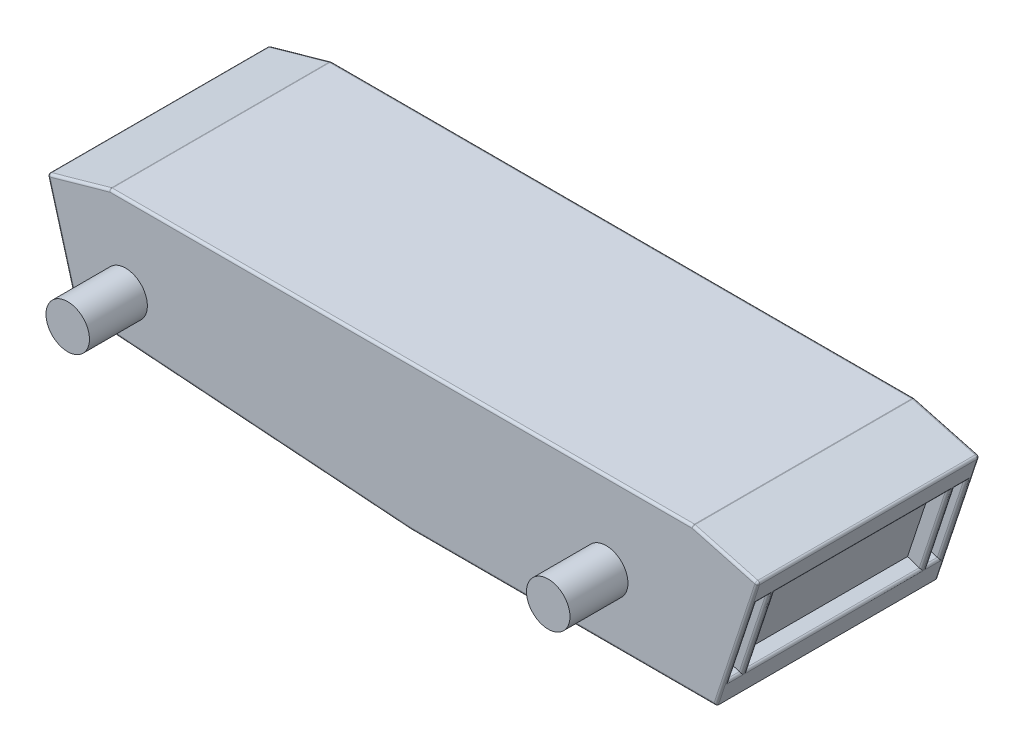
SolidWorks part; units mm, degrees
ref_plane "Front Plane" through (0, 0, 0) normal (0, 0, 1) x (1, 0, 0)
ref_plane "Top Plane" through (0, 0, 0) normal (0, 1, 0) x (1, 0, 0)
ref_plane "Right Plane" through (0, 0, 0) normal (1, 0, 0) x (0, 0, -1)
sketch "Sketch1" plane through (0, 0, 0) normal (0, 0, 1) x (1, 0, 0)
  line L0 (-342.4568, 3.8221) -> (442.8765, 3.8221) construction
sketch "Sketch2" plane through (0, 0, 0) normal (1, 0, 0) x (0, 0, -1)
  line L0 (-168.6601, 20.0355) -> (30.6732, 20.0355) construction
sketch "Sketch3" plane through (0, 0, 0) normal (0, 0, 1) x (1, 0, 0)
  line L0 (412.3453, 143.1765) -> (343.4293, 161.6913)
  line L1 (343.4293, 161.6913) -> (-269.6146, 161.6913)
  line L2 (-269.6146, 161.6913) -> (-335.4449, 143.1765)
  line L3 (-335.4449, 143.1765) -> (-304.9165, 34.6311)
  line L4 (-304.9165, 34.6311) -> (47.1933, 9.4589)
  line L5 (47.1933, 9.4589) -> (368.1156, 9.4589)
  line L6 (368.1156, 9.4589) -> (412.3453, 143.1765)
extrude "Boss-Extrude1" add sketch "Sketch3" along normal blind 116.84 and the other way blind 116.84
sketch "Sketch4" plane through (328.9924, -108.8206, 0) normal (0.9494, -0.314, 0) x (0, 0, -1)
  line L0 (-97.79, 240.0246) -> (-110.49, 240.0246)
  line L2 (-110.49, 240.0246) -> (-104.14, 240.0246)
  line L3 (-110.49, 240.0246) -> (-110.49, 149.9819)
  line L4 (-97.79, 149.9819) -> (-110.49, 149.9819)
  line L5 (-104.14, 240.0246) -> (-97.79, 240.0246)
  line L6 (-97.79, 240.0246) -> (-97.79, 149.9819)
  line L7 (-97.79, 149.9819) -> (-110.49, 149.9819)
  line L8 (0, 485.65) -> (0, -485.65) construction
  line L9 (97.79, 149.9819) -> (110.49, 149.9819)
  line L10 (110.49, 240.0246) -> (110.49, 149.9819)
  line L11 (97.79, 240.0246) -> (110.49, 240.0246)
  line L12 (97.79, 240.0246) -> (97.79, 149.9819)
  line L24 (-91.44, 149.9819) -> (91.44, 149.9819)
  line L25 (-91.44, 240.0246) -> (-91.44, 149.9819)
  line L26 (91.44, 149.9819) -> (91.44, 240.0246)
  line L27 (91.44, 240.0246) -> (-91.44, 240.0246)
  line L28 (-91.44, 149.9819) -> (91.44, 149.9819)
  line L29 (-91.44, 240.0246) -> (-91.44, 149.9819)
  line L30 (91.44, 149.9819) -> (91.44, 240.0246)
  line L31 (91.44, 240.0246) -> (-91.44, 240.0246)
  dimension "D1" = 25.4
extrude "Cut-Extrude1" cut sketch "Sketch4" against normal blind 15.494 contours L30 L31 L29 L28 | L6 L0 L3 L4 | L12 L9 L10 L11 region at (390.2305, 76.3177, 104.14) region at (390.2305, 76.3177, 0)
fillet "Fillet1" radius 2.54 16 edges at (375.5203, 81.1834, -110.49) (361.382, 38.4396, -104.14) (375.5203, 81.1834, -97.79) (389.6586, 123.9272, -104.14) (361.382, 38.4396, 104.14) (375.5203, 81.1834, 110.49) (389.6586, 123.9272, 104.14) (375.5203, 81.1834, 97.79) (390.2305, 76.3177, -97.79) (376.0921, 33.5739, -104.14) (404.3688, 119.0615, -104.14) (390.2305, 76.3177, -110.49) (376.0921, 33.5739, 104.14) (390.2305, 76.3177, 110.49) (390.2305, 76.3177, 97.79) (404.3688, 119.0615, 104.14)
fillet "Fillet2" radius 2.54 4 edges at (404.3688, 119.0615, 0) (390.2305, 76.3177, 91.44) (376.0921, 33.5739, 0) (390.2305, 76.3177, -91.44)
sketch "Sketch5" plane through (0, 0, 0) normal (0, 0, 1) x (1, 0, 0)
  line L35 (379.7858, 125.6232) -> (340.0768, 136.2913)
  line L36 (349.7637, 34.8589) -> (379.7858, 125.6232)
  line L37 (48.1001, 34.8589) -> (349.7637, 34.8589)
  line L38 (-285.2985, 58.6935) -> (48.1001, 34.8589)
  line L39 (-304.1166, 125.6021) -> (-285.2985, 58.6935)
  line L40 (-266.1107, 136.2913) -> (-304.1166, 125.6021)
  line L41 (340.0768, 136.2913) -> (-266.1107, 136.2913)
  line L42 (379.7858, 125.6232) -> (340.0768, 136.2913)
  line L43 (349.7637, 34.8589) -> (379.7858, 125.6232)
  line L44 (48.1001, 34.8589) -> (349.7637, 34.8589)
  line L45 (-285.2985, 58.6935) -> (48.1001, 34.8589)
  line L46 (-304.1166, 125.6021) -> (-285.2985, 58.6935)
  line L47 (-266.1107, 136.2913) -> (-304.1166, 125.6021)
  line L48 (340.0768, 136.2913) -> (-266.1107, 136.2913)
  dimension "D1" = 25.4
extrude "Cut-Extrude2" cut sketch "Sketch5" against normal blind 101.6 and the other way blind 101.6 contours L42 L48 L47 L46 L45 L44 L43
fillet "Fillet3" radius 2.54 21 edges at (412.3453, 143.1765, 0) (343.4293, 161.6913, 0) (-269.6146, 161.6913, 0) (-335.4449, 143.1765, 0) (-304.9165, 34.6311, 0) (207.6545, 9.4589, 116.84) (-128.8616, 22.045, 116.84) (-320.1807, 88.9038, 116.84) (-302.5297, 152.4339, 116.84) (36.9073, 161.6913, 116.84) (377.8873, 152.4339, 116.84) (390.2305, 76.3177, 116.84) (377.8873, 152.4339, -116.84) (36.9073, 161.6913, -116.84) (-302.5297, 152.4339, -116.84) (-320.1807, 88.9038, -116.84) (-128.8616, 22.045, -116.84) (207.6545, 9.4589, -116.84) (390.2305, 76.3177, -116.84) (47.1933, 9.4589, 0) (48.1001, 34.8589, 0)
sketch "Sketch6" plane through (-273.5391, -76.9329, 0) normal (-0.9627, -0.2707, 0) x (0, 0, 1)
  line L8 (-88.9, 143.0777) -> (88.9, 143.0777)
  line L9 (88.9, 143.0777) -> (88.9, 200.7092)
  line L10 (88.9, 200.7092) -> (-88.9, 200.7092)
  line L11 (-88.9, 200.7092) -> (-88.9, 143.0777)
  line L12 (-88.9, 143.0777) -> (88.9, 143.0777)
  line L13 (88.9, 143.0777) -> (88.9, 200.7092)
  line L14 (88.9, 200.7092) -> (-88.9, 200.7092)
  line L15 (-88.9, 200.7092) -> (-88.9, 143.0777)
  dimension "D1" = 25.4
extrude "Cut-Extrude3" cut sketch "Sketch6" against normal blind 13.97 contours L12 L13 L14 L15
fillet "Fillet4" radius 2.54 8 edges at (-314.432, 120.0624, 0) (-306.6302, 92.3229, 88.9) (-298.8285, 64.5833, 0) (-306.6302, 92.3229, -88.9) (-312.2767, 60.801, 0) (-320.0785, 88.5405, 88.9) (-327.8802, 116.2801, 0) (-320.0785, 88.5405, -88.9)
sketch "Sketch8" plane through (0, 0, 0) normal (0, 0, 1) x (1, 0, 0)
  line L0 (0, -485.65) -> (0, 485.65) construction
  circle A0 centre (-252.7288, 75.375) radius 22.86
  circle A1 centre (252.7288, 75.375) radius 22.86
extrude "Boss-Extrude3" add sketch "Sketch8" along normal blind 177.8 and the other way blind 177.8
sketch "Sketch9" plane through (0, 0, -116.84) normal (0, 0, -1) x (-1, 0, 0)
  line L0 (95.3411, 123.152) -> (165.217, 123.152)
  line L1 (165.217, 123.152) -> (165.217, 103.9608)
  line L2 (165.217, 103.9608) -> (-65.5702, 103.9608)
  line L3 (-65.5702, 103.9608) -> (-65.5702, 123.152)
  line L4 (-65.5702, 123.152) -> (165.217, 123.152)
extrude "Cut-Extrude4" cut sketch "Sketch9" against normal blind 118.364 contours L4 L3 L2 L1 L0 region at (-49.8234, 113.5564, -116.84)
